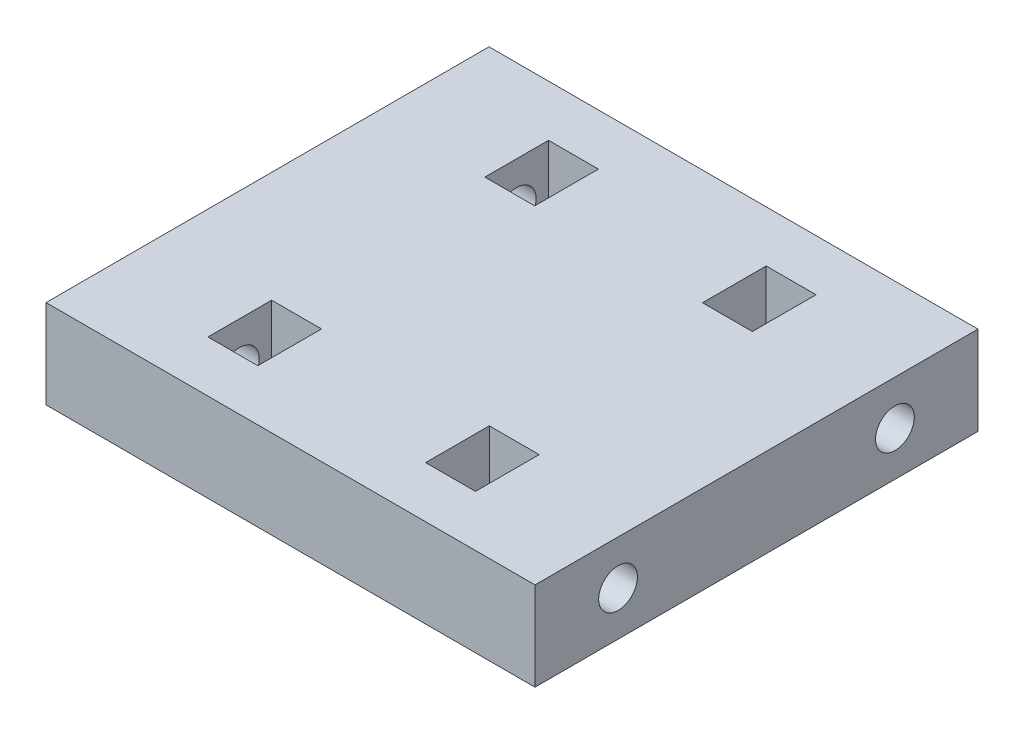
SolidWorks part; units mm, degrees
ref_plane "Front Plane" through (0, 0, 0) normal (0, 0, 1) x (1, 0, 0)
ref_plane "Top Plane" through (0, 0, 0) normal (0, 1, 0) x (1, 0, 0)
ref_plane "Right Plane" through (0, 0, 0) normal (1, 0, 0) x (0, 0, -1)
sketch "Sketch1" plane through (0, 0, 0) normal (1, 0, 0) x (0, 0, -1)
  line L1 (-20, 4) -> (20, 4)
  line L2 (-20, 4) -> (-20, -4)
  line L3 (-20, -4) -> (20, -4)
  line L4 (20, 4) -> (20, -4)
  line L5 (-20, 4) -> (20, -4) construction
  line L6 (-20, -4) -> (20, 4) construction
  point P0 (0, 0)
  dimension "D1" = 40
  dimension "D2" = 8
extrude "Boss-Extrude1" add sketch "Sketch1" along normal mid plane 44.15
sketch "Sketch2" plane through (22.075, 0, 0) normal (1, 0, 0) x (0, 0, -1)
  line L0 (0, 4) -> (0, -4) construction
  line L1 (20, 4) -> (-20, 4) construction
  line L2 (-20, -4) -> (20, -4) construction
  line L3 (-20, 0) -> (20, 0) construction
  line L4 (-20, 4) -> (-20, -4) construction
  line L5 (20, -4) -> (20, 4) construction
  circle A0 centre (-12.5, 0) radius 1.75
  circle A1 centre (12.5, 0) radius 1.75
  dimension "D2" = 3.5
  dimension "D1" = 25
extrude "Cut-Extrude1" cut sketch "Sketch2" against normal blind 10
ref_plane "Plane1" through (12.075, 0, 0) normal (1, 0, 0) x (0, 0, -1)
sketch "Sketch3" plane through (12.075, 0, 0) normal (1, 0, 0) x (0, 0, -1)
  line L0 (-15.375, 1.6599) -> (-15.375, 4)
  line L1 (-15.375, -1.6599) -> (-12.5, -3.3198)
  line L2 (-12.5, -3.3198) -> (-9.625, -1.6599)
  line L3 (-9.625, -1.6599) -> (-9.625, 1.6599)
  line L4 (-9.625, 1.6599) -> (-12.5, 3.3198)
  line L5 (-12.5, 3.3198) -> (-15.375, 1.6599)
  line L6 (-15.375, 1.6599) -> (-15.375, -1.6599)
  line L7 (20, 4) -> (-20, 4) construction
  line L8 (-15.375, 4) -> (-9.625, 4)
  line L9 (-9.625, 4) -> (-9.625, 1.6599)
  line L10 (0, 4) -> (0, -4) construction
  line L11 (-20, -4) -> (20, -4) construction
  line L12 (9.625, 4) -> (9.625, 1.6599)
  line L13 (15.375, 4) -> (9.625, 4)
  line L14 (15.375, 1.6599) -> (15.375, 4)
  line L15 (9.625, -1.6599) -> (9.625, 1.6599)
  line L16 (12.5, -3.3198) -> (9.625, -1.6599)
  line L17 (15.375, -1.6599) -> (12.5, -3.3198)
  line L18 (15.375, 1.6599) -> (15.375, -1.6599)
  circle A0 centre (-12.5, 0) radius 2.875 construction
  dimension "D1" = 5.75
extrude "Cut-Extrude2" cut sketch "Sketch3" against normal blind 4.5 contours L5 L6 L1 L2 L3 L4 | L9 L8 L0 L5 L4 | L18 L14 L13 L12 L15 L16 L17 region at (12.075, 2.8299, 15.3129) region at (12.075, 0, 12.5) region at (12.075, 0.7374, -12.5)
mirror "Mirror1" about plane through (0, 0, 0) normal (1, 0, 0) of "Cut-Extrude2", "Cut-Extrude1"
